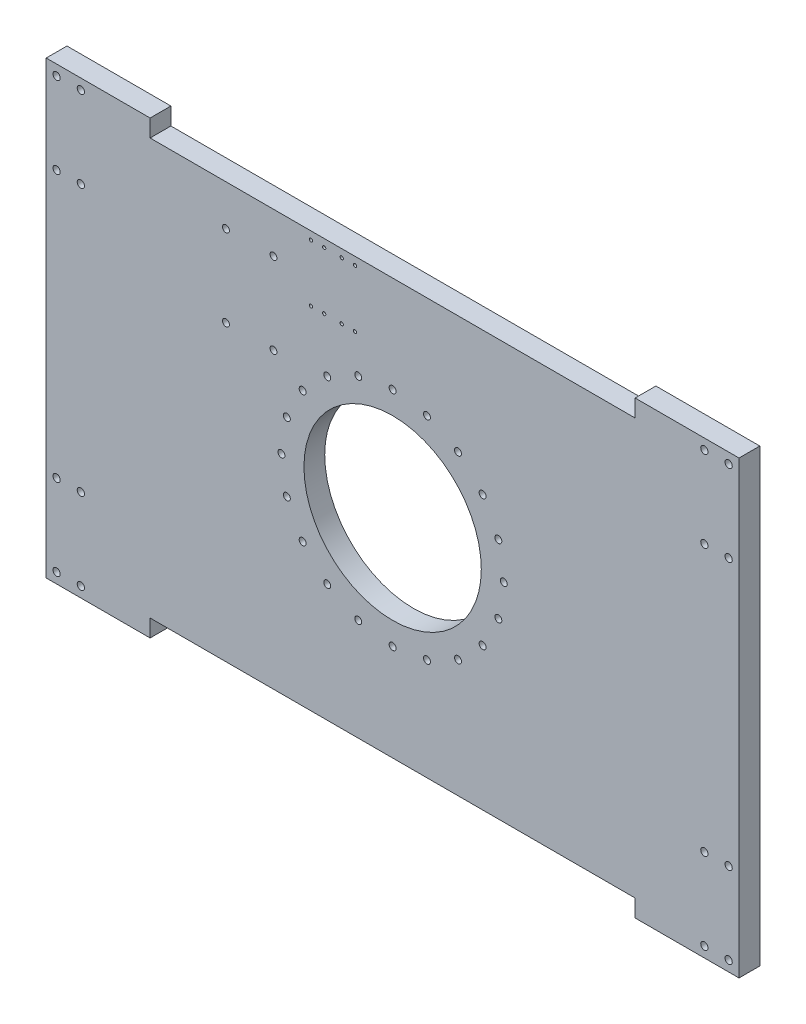
SolidWorks part; units mm, degrees
material "ASTM A36 Acier"
ref_plane "Plan de face" through (0, 0, 0) normal (0, 0, 1) x (1, 0, 0)
ref_plane "Plan de dessus" through (0, 0, 0) normal (0, 1, 0) x (1, 0, 0)
ref_plane "Plan de droite" through (0, 0, 0) normal (1, 0, 0) x (0, 0, -1)
sketch "Esquisse1" plane through (0, 0, 0) normal (0, 0, 1) x (1, 0, 0)
  line L0 (-1000, 1250) -> (-700, 1250)
  line L1 (-700, 1250) -> (-700, 1200)
  line L2 (-700, 1200) -> (700, 1200)
  line L3 (700, 1200) -> (700, 1250)
  line L4 (700, 1250) -> (1000, 1250)
  line L5 (1000, 1250) -> (1000, -50)
  line L6 (1000, -50) -> (700, -50)
  line L7 (700, -50) -> (700, 0)
  line L8 (700, 0) -> (-700, 0)
  line L9 (-700, 0) -> (-700, -50)
  line L10 (-700, -50) -> (-1000, -50)
  line L11 (-1000, -50) -> (-1000, 1250)
  line L13 (-970, -20) -> (-900, -20) construction
  line L14 (-970, -20) -> (-970, 215) construction
  line L15 (-970, 215) -> (-900, 215) construction
  line L16 (-900, -20) -> (-900, 215) construction
  circle A0 centre (-970, -20) radius 10.5
  circle A1 centre (-970, 215) radius 10.5
  circle A2 centre (-900, 215) radius 10.5
  circle A3 centre (-900, -20) radius 10.5
  point P15 (0, 0)
  dimension "D3" = 30
  dimension "D14" = 21
  dimension "D15" = 21
  dimension "D16" = 21
  dimension "D17" = 21
  dimension "D1" = 2000
  dimension "D2" = 50
  dimension "D4" = 300
  dimension "D5" = 300
  dimension "D6" = 300
  dimension "D7" = 300
  dimension "D8" = 1200
  dimension "D9" = 50
  dimension "D10" = 1400
  dimension "D11" = 30
  dimension "D12" = 70
  dimension "D13" = 235
extrude "Boss.-Extru.1" add sketch "Esquisse1" along normal blind 60
sketch "Esquisse2" plane through (0, 0, 60) normal (0, 0, 1) x (1, 0, 0)
  line L0 (700, -50) -> (1000, -50) construction
  circle A0 centre (0, 600) radius 256
  dimension "D1" = 512
  dimension "D2" = 650
extrude "Enlèv. mat.-Extru.1" cut sketch "Esquisse2" against normal through all
sketch "Esquisse4" plane through (0, 0, 0) normal (1, 0, 0) x (0, 0, -1)
  line L0 (0, 600) -> (1429.3387, 600) construction
  dimension "D1" = 600
sketch "Esquisse5" plane through (0, 0, 0) normal (0, 0, 1) x (1, 0, 0)
  circle A0 centre (0, 921) radius 10
  circle A1 centre (0, 600) radius 256 construction
  dimension "D1" = 20
  dimension "D2" = 321
extrude "Enlèv. mat.-Extru.3" cut sketch "Esquisse5" along normal through all
pattern_circular "Répétition circulaire1" count 20 every 18 about axis through (0, 600, 0) along (0, 0, -1) of "Enlèv. mat.-Extru.3"
ref_plane "Plan1" through (0, 0, 0) normal (0, 0, -1) x (-1, 0, 0)
ref_plane "Plan2" through (-1000, -50, 60) normal (0, -1, 0) x (-1, 0, 0)
ref_plane "Plan7" through (-514.2059, 810, 60) normal (1, 0, 0) x (0, 0, -1)
sketch "Esquisse11" plane through (0, 0, 0) normal (0, 0, -1) x (-1, 0, 0)
  circle A0 centre (343.85, 847.5) radius 10
  circle A1 centre (481.15, 847.5) radius 10
  circle A2 centre (481.15, 1082.5) radius 10
  circle A3 centre (343.85, 1082.5) radius 10
extrude "Enlèv. mat.-Extru.5" cut sketch "Esquisse11" against normal blind 100 and the other way through all
sketch "Esquisse12" plane through (0, 0, 0) normal (0, 0, -1) x (-1, 0, 0)
  circle A0 centre (108.7481, 1177.1251) radius 4.7625
  circle A1 centre (197.6481, 1177.1251) radius 4.7625
  circle A2 centre (108.7481, 1012.0251) radius 4.7625
  circle A3 centre (146.8481, 1012.0251) radius 4.7625
  circle A4 centre (197.6481, 1012.0251) radius 4.7641
  circle A5 centre (235.7481, 1012.0251) radius 4.7625
  circle A6 centre (235.7481, 1177.1251) radius 4.7625
  circle A7 centre (146.8481, 1177.1251) radius 4.7625
extrude "Enlèv. mat.-Extru.6" cut sketch "Esquisse12" against normal blind 100
sketch "Esquisse15" plane through (0, 0, 0) normal (0, 0, -1) x (-1, 0, 0)
  line L0 (1000, 1250) -> (1000, -50) construction
  line L5 (700, 1250) -> (1000, 1250) construction
  circle A0 centre (970, 1220) radius 10.5
  circle A1 centre (970, 985) radius 10.5
  circle A2 centre (900, 985) radius 10.5
  circle A3 centre (900, 1220) radius 10.5
  dimension "D1" = 21
  dimension "D4" = 30
  dimension "D2" = 235
  dimension "D3" = 70
  dimension "D5" = 30
  dimension "D6" = 30
  dimension "D7" = 100
extrude "Enlèv. mat.-Extru.7" cut sketch "Esquisse15" against normal blind 110
mirror "Symétrie1" about plane through (0, 0, 0) normal (1, 0, 0) of "Enlèv. mat.-Extru.7"
sketch "Esquisse16" plane through (0, 0, 0) normal (0, 0, -1) x (-1, 0, 0)
  line L0 (-700, -50) -> (-1000, -50) construction
  line L5 (-1000, -50) -> (-1000, 1250) construction
  circle A0 centre (-970, -20) radius 10.5
  circle A1 centre (-900, -20) radius 10.5
  circle A2 centre (-900, 215) radius 10.5
  circle A3 centre (-970, 215) radius 10.5
  dimension "D1" = 235
  dimension "D3" = 30
  dimension "D2" = 70
  dimension "D4" = 0
  dimension "D5" = 30
extrude "Enlèv. mat.-Extru.8" cut sketch "Esquisse16" against normal blind 110
